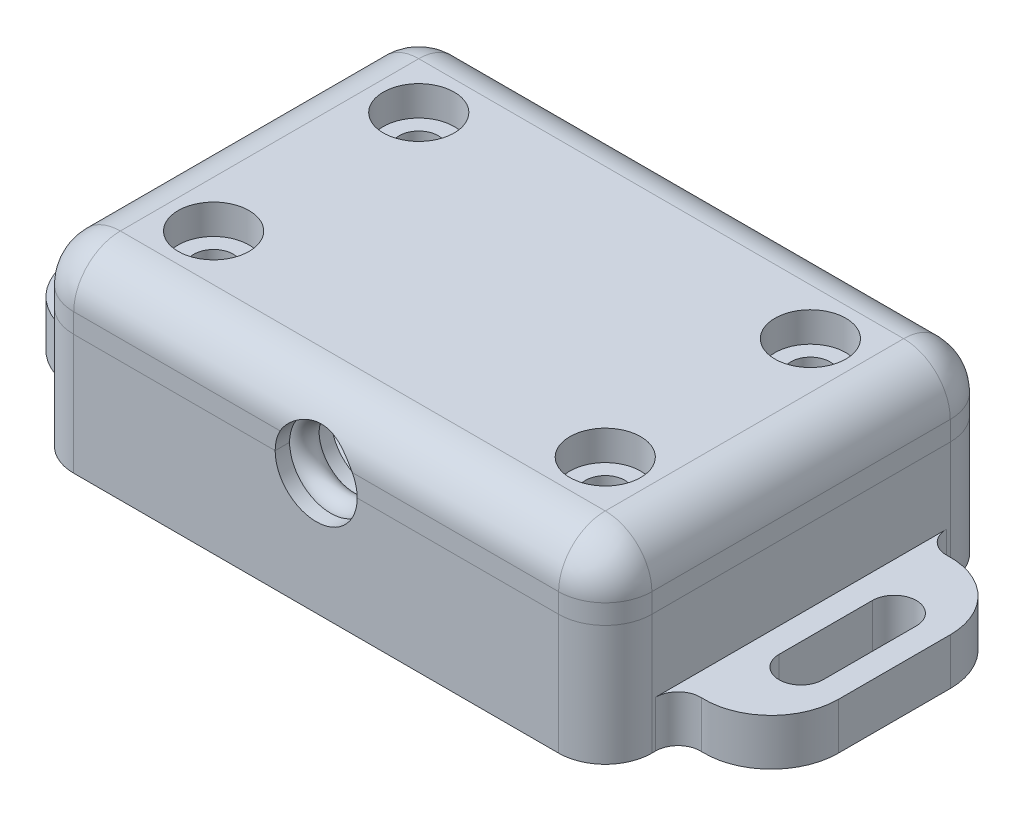
SolidWorks part; units mm, degrees
ref_plane "Front Plane" through (0, 0, 0) normal (0, 0, 1) x (1, 0, 0)
ref_plane "Top Plane" through (0, 0, 0) normal (0, 1, 0) x (1, 0, 0)
ref_plane "Right Plane" through (0, 0, 0) normal (1, 0, 0) x (0, 0, -1)
sketch "Sketch1" plane through (0, 0, 0) normal (0, 1, 0) x (1, 0, 0)
  line L5 (-15.875, -9.525) -> (15.875, -9.525)
  line L6 (-15.875, -9.525) -> (-15.875, 9.525)
  line L7 (-15.875, 9.525) -> (15.875, 9.525)
  line L8 (15.875, -9.525) -> (15.875, 9.525)
  line L9 (-15.875, -9.525) -> (15.875, 9.525) construction
  line L10 (-15.875, 9.525) -> (15.875, -9.525) construction
  line L11 (-19.685, -13.335) -> (19.685, -13.335)
  line L12 (-19.685, -13.335) -> (-19.685, 13.335)
  line L13 (-19.685, 13.335) -> (19.685, 13.335)
  line L14 (19.685, -13.335) -> (19.685, 13.335)
  line L15 (-19.685, -13.335) -> (19.685, 13.335) construction
  line L16 (-19.685, 13.335) -> (19.685, -13.335) construction
  point P0 (0, 0)
  point P6 (0, 0)
  dimension "D1" = 3.81
  dimension "D2" = 3.81
  dimension "D3" = 31.75
  dimension "D4" = 19.05
extrude "Boss-Extrude1" add sketch "Sketch1" along normal blind 4.2543
sketch "Sketch3" plane through (0, 0, 13.335) normal (0, 0, 1) x (1, 0, 0)
  line L0 (-19.685, 4.2543) -> (19.685, 4.2543) construction
  circle A0 centre (0, 4.2543) radius 2.794
  dimension "D1" = 5.588
extrude "Cut-Extrude1" cut sketch "Sketch3" against normal up to next
mirror "Mirror1" about plane through (0, 4.2543, 0) normal (0, -1, 0) of bodies 103
sketch "Sketch2" plane through (0, 0, 0) normal (0, -1, 0) x (1, 0, 0)
  line L0 (-19.685, 13.335) -> (19.685, 13.335) construction
  line L1 (19.685, -13.335) -> (-19.685, -13.335)
  line L2 (19.685, -13.335) -> (19.685, 13.335)
  line L3 (19.685, 13.335) -> (-19.685, 13.335)
  line L4 (-19.685, -13.335) -> (-19.685, 13.335)
  line L5 (19.685, -13.335) -> (-19.685, 13.335) construction
  line L6 (19.685, 13.335) -> (-19.685, -13.335) construction
  line L7 (-19.685, -13.335) -> (-19.685, 13.335) construction
  point P0 (0, 0)
extrude "Boss-Extrude2" add sketch "Sketch2" along normal blind 3.937
sketch "Sketch4" plane through (0, 4.2543, 0) normal (0, 1, 0) x (1, 0, 0)
  line L0 (2.794, -11.43) -> (16.51, -11.43)
  line L1 (2.794, -13.335) -> (2.794, -9.525) construction
  line L2 (17.78, -10.16) -> (17.78, 10.16)
  line L3 (16.51, 11.43) -> (-16.51, 11.43)
  line L4 (-17.78, 10.16) -> (-17.78, -10.16)
  line L5 (-16.51, -11.43) -> (-2.794, -11.43)
  line L6 (-2.794, -9.525) -> (-2.794, -13.335) construction
  line L7 (15.875, -9.525) -> (15.875, -11.43) construction
  line L8 (15.875, -11.43) -> (15.875, -9.525) construction
  line L9 (15.875, -9.525) -> (17.78, -9.525) construction
  line L10 (15.875, 9.525) -> (15.875, 11.43) construction
  line L11 (-15.875, 9.525) -> (-17.78, 9.525) construction
  arc A0 (16.51, -11.43) -> (17.78, -10.16) centre (16.51, -10.16) ccw
  arc A1 (-17.78, -10.16) -> (-16.51, -11.43) centre (-16.51, -10.16) ccw
  arc A2 (-16.51, 11.43) -> (-17.78, 10.16) centre (-16.51, 10.16) ccw
  arc A3 (17.78, 10.16) -> (16.51, 11.43) centre (16.51, 10.16) ccw
  dimension "D1" = 1.27
ref_plane "Plane1" through (2.794, 0, 0) normal (-1, 0, 0) x (0, 0, 1)
sketch "Sketch5" plane through (2.794, 0, 0) normal (-1, 0, 0) x (0, 0, 1)
  line L0 (13.335, 4.2543) -> (9.525, 4.2543) construction
  circle A0 centre (11.43, 4.2543) radius 0.9525
  dimension "D1" = 1.905
sketch "Sketch6" plane through (0, 4.2543, 0) normal (0, 1, 0) x (1, 0, 0)
  line L0 (-17.78, 10.16) -> (-17.78, -10.16) construction
  line L5 (16.51, 11.43) -> (-16.51, 11.43) construction
  line L6 (17.78, -10.16) -> (17.78, 10.16) construction
  line L7 (-17.78, 10.16) -> (-17.78, -10.16)
  line L8 (16.51, 11.43) -> (-16.51, 11.43)
  line L9 (17.78, -10.16) -> (17.78, 10.16)
  line L10 (-16.51, -11.43) -> (16.51, -11.43)
  arc A0 (-17.78, -10.16) -> (-16.51, -11.43) centre (-16.51, -10.16) ccw construction
  arc A1 (-16.51, 11.43) -> (-17.78, 10.16) centre (-16.51, 10.16) ccw construction
  arc A2 (17.78, 10.16) -> (16.51, 11.43) centre (16.51, 10.16) ccw construction
  arc A3 (16.51, -11.43) -> (17.78, -10.16) centre (16.51, -10.16) ccw construction
  arc A4 (-17.78, -10.16) -> (-16.51, -11.43) centre (-16.51, -10.16) ccw
  arc A5 (-16.51, 11.43) -> (-17.78, 10.16) centre (-16.51, 10.16) ccw
  arc A6 (17.78, 10.16) -> (16.51, 11.43) centre (16.51, 10.16) ccw
  arc A7 (16.51, -11.43) -> (17.78, -10.16) centre (16.51, -10.16) ccw
sweep "Cut-Sweep2" cut profiles "Sketch5" path "Sketch6"
sketch "Sketch7" plane through (0, 4.2543, 0) normal (0, 1, 0) x (1, 0, 0)
  line L0 (2.794, -10.4775) -> (16.51, -10.4775) construction
  line L1 (16.51, -12.3825) -> (2.794, -12.3825) construction
  line L2 (2.794, -10.4775) -> (2.794, -9.525) construction
  circle A0 centre (3.048, -11.43) radius 0.9525
  point P6 (3.1533, -13.906)
  dimension "D1" = 0.254
ref_axis "Axis1" through (0, 4.2543, 9.525) along (0, 0, 1)
revolve "Cut-Revolve1" cut sketch "Sketch7" angle 360 about axis through (0, 4.2543, 9.525) along (0, 0, 1)
sweep "Sweep1" add profiles "Sketch5<2>" path "Sketch4"
sketch "Sketch5<2>" plane through (2.794, 0, 0) normal (-1, 0, 0) x (0, 0, 1) same geometry as "Sketch5"
revolve "Revolve1" add sketch "Sketch7<2>" angle 360 about axis through (0, 4.2543, 9.525) along (0, 0, 1)
sketch "Sketch7<2>" plane through (0, 4.2543, 0) normal (0, 1, 0) x (1, 0, 0) same geometry as "Sketch7"
ref_plane "Top of PCB" through (0, 1.6, 0) normal (0, 1, 0) x (1, 0, 0)
sketch "Sketch9" plane through (0, 8.5086, 0) normal (0, 1, 0) x (1, 0, 0)
  line L0 (-19.685, -13.335) -> (19.685, -13.335) construction
  line L1 (19.685, 13.335) -> (-19.685, 13.335)
  line L2 (19.685, 13.335) -> (19.685, -13.335)
  line L3 (19.685, -13.335) -> (-19.685, -13.335)
  line L4 (-19.685, 13.335) -> (-19.685, -13.335)
  line L5 (19.685, 13.335) -> (-19.685, -13.335) construction
  line L6 (19.685, -13.335) -> (-19.685, 13.335) construction
  line L7 (-19.685, 13.335) -> (-19.685, -13.335) construction
  point P0 (0, 0)
extrude "Boss-Extrude3" add sketch "Sketch9" along normal blind 0.254
sketch "Sketch13" plane through (0, 8.5086, 0) normal (0, -1, 0) x (1, 0, 0)
  line L1 (15.875, -9.525) -> (-15.875, -9.525)
  line L2 (15.875, -9.525) -> (15.875, 9.525)
  line L3 (15.875, 9.525) -> (-15.875, 9.525)
  line L4 (-15.875, -9.525) -> (-15.875, 9.525)
  line L5 (15.875, -9.525) -> (-15.875, 9.525) construction
  line L6 (15.875, 9.525) -> (-15.875, -9.525) construction
  point P0 (0, 0)
extrude "Boss-Extrude5" add sketch "Sketch13" along normal blind 1.6
sketch "Sketch10" plane through (0, 6.9086, 0) normal (0, -1, 0) x (1, 0, 0)
  line L1 (15.875, -9.525) -> (-15.875, -9.525) construction
  line L2 (0, 0) -> (0, -50000) construction
  line L3 (0, 0) -> (-50000, 0) construction
  line L8 (13.335, -3.937) -> (15.875, -3.937)
  line L9 (10.287, -6.985) -> (10.287, -9.525)
  line L10 (10.287, -9.525) -> (15.875, -9.525)
  line L11 (15.875, -9.525) -> (15.875, -3.937)
  line L12 (-15.875, -9.525) -> (-15.875, -3.937)
  line L13 (-10.287, -9.525) -> (-15.875, -9.525)
  line L14 (-10.287, -6.985) -> (-10.287, -9.525)
  line L15 (-13.335, -3.937) -> (-15.875, -3.937)
  line L16 (-13.335, 3.937) -> (-15.875, 3.937)
  line L17 (-10.287, 6.985) -> (-10.287, 9.525)
  line L18 (-10.287, 9.525) -> (-15.875, 9.525)
  line L19 (-15.875, 9.525) -> (-15.875, 3.937)
  line L20 (15.875, 9.525) -> (15.875, 3.937)
  line L21 (10.287, 9.525) -> (15.875, 9.525)
  line L22 (10.287, 6.985) -> (10.287, 9.525)
  line L23 (13.335, 3.937) -> (15.875, 3.937)
  line L24 (15.875, 9.525) -> (15.875, -9.525) construction
  arc A0 (13.335, -3.937) -> (10.287, -6.985) centre (13.335, -6.985) ccw
  arc A1 (-13.335, -3.937) -> (-10.287, -6.985) centre (-13.335, -6.985) cw
  arc A2 (-13.335, 3.937) -> (-10.287, 6.985) centre (-13.335, 6.985) ccw
  arc A3 (13.335, 3.937) -> (10.287, 6.985) centre (13.335, 6.985) cw
  dimension "D3" = 3.048
  dimension "D1" = 2.54
  dimension "D2" = 2.54
extrude "Boss-Extrude4" add sketch "Sketch10" along normal up to surface (5.3086 mm away) up to plane "Top of PCB"
sketch "Sketch11" plane through (0, 1.6, 0) normal (0, -1, 0) x (1, 0, 0)
  line L0 (0, 0) -> (0, 50000) construction
  line L1 (0, 0) -> (50000, 0) construction
  circle A0 centre (13.335, 6.985) radius 1.3335
  circle A2 centre (13.335, -6.985) radius 1.3335
  circle A3 centre (-13.335, 6.985) radius 1.3335
  circle A4 centre (-13.335, -6.985) radius 1.3335
  arc A5 (10.287, 6.985) -> (13.335, 3.937) centre (13.335, 6.985) ccw construction
  dimension "D1" = 2.667
extrude "Cut-Extrude2" cut sketch "Sketch11" against normal through all
sketch "Sketch12" plane through (0, 8.7626, 0) normal (0, 1, 0) x (1, 0, 0)
  line L0 (0, 0) -> (0, -50000) construction
  line L1 (0, 0) -> (-50000, 0) construction
  circle A0 centre (-13.335, -6.985) radius 2.413
  circle A1 centre (-13.335, -6.985) radius 1.3335 construction
  circle A2 centre (-13.335, 6.985) radius 2.413
  circle A3 centre (13.335, -6.985) radius 2.413
  circle A4 centre (13.335, 6.985) radius 2.413
  dimension "D1" = 4.826
extrude "Cut-Extrude3" cut sketch "Sketch12" against normal blind 2.032
fillet "Fillet2" radius 3.175 8 edges at (19.685, 6.5085, -13.335) (-19.685, 6.5085, -13.335) (-19.685, 6.5085, 13.335) (19.685, 6.5085, 13.335) (19.685, 8.7626, 0) (0, 8.7626, -13.335) (-19.685, 8.7626, 0) (0, 8.7626, 13.335)
fillet "Fillet3" radius 3.175 12 edges at (10.287, 6.9086, 8.255) (14.605, 6.9086, 3.937) (14.605, 6.9086, -3.937) (10.287, 6.9086, -8.255) (-14.605, 6.9086, 3.937) (-10.287, 6.9086, 8.255) (-14.605, 6.9086, -3.937) (-11.1797, 6.9086, -4.8297) (11.1797, 6.9086, 4.8297) (11.1797, 6.9086, -4.8297) (-11.1797, 6.9086, 4.8297) (-10.287, 6.9086, -8.255)
fillet "Fillet4" radius 0.508 8 edges at (-13.081, 1.6, -9.525) (-15.875, 1.6, -6.731) (-15.875, 1.6, 6.731) (-13.081, 1.6, 9.525) (15.875, 1.6, 6.731) (13.081, 1.6, 9.525) (15.875, 1.6, -6.731) (13.081, 1.6, -9.525)
extrude "Cut-Extrude5" cut sketch "Sketch11<2>" along normal blind 4.572 draft 4
sketch "Sketch11<2>" plane through (0, 1.6, 0) normal (0, -1, 0) x (1, 0, 0) same geometry as "Sketch11"
fillet "Fillet5" radius 3.175 4 edges at (-19.685, 0.1586, -13.335) (-19.685, 0.1586, 13.335) (19.685, 0.1586, -13.335) (19.685, 0.1586, 13.335)
sketch "Sketch14" plane through (0, -3.937, 0) normal (0, -1, 0) x (1, 0, 0)
  line L0 (19.685, 9.9007) -> (19.685, -9.9007)
  line L1 (19.685, -10.16) -> (19.685, 10.16) construction
  line L3 (0, 0) -> (50000, 0) construction
  line L4 (26.035, -3.81) -> (26.035, 3.81)
  line L5 (22.86, 3.175) -> (22.86, -3.175) construction
  line L6 (24.36, 3.175) -> (24.36, -3.175)
  line L7 (21.36, 3.175) -> (21.36, -3.175)
  line L8 (22.86, -1.0957) -> (19.685, -1.0957) construction
  line L9 (19.685, -1.0957) -> (22.86, -1.0957) construction
  line L10 (22.86, -1.0957) -> (26.035, -1.0957) construction
  line L11 (0, 0) -> (0, 50000) construction
  line L12 (-22.86, 3.175) -> (-22.86, -3.175) construction
  line L13 (-24.36, 3.175) -> (-24.36, -3.175)
  line L14 (-21.36, 3.175) -> (-21.36, -3.175)
  line L15 (-22.86, -1.0957) -> (-26.035, -1.0957) construction
  line L16 (-19.685, -1.0957) -> (-22.86, -1.0957) construction
  line L17 (-22.86, -1.0957) -> (-19.685, -1.0957) construction
  line L18 (-26.035, -3.81) -> (-26.035, 3.81)
  line L19 (-19.685, 9.9007) -> (-19.685, -9.9007)
  arc A0 (19.685, -9.9007) -> (21.2725, -8.378) centre (21.209, -9.9007) cw
  arc A3 (21.2725, -8.378) -> (26.035, -3.81) centre (21.463, -3.81) ccw
  arc A4 (21.2725, 8.378) -> (26.035, 3.81) centre (21.463, 3.81) cw
  arc A5 (19.685, 9.9007) -> (21.2725, 8.378) centre (21.209, 9.9007) ccw
  arc A6 (24.36, 3.175) -> (21.36, 3.175) centre (22.86, 3.175) ccw
  arc A7 (21.36, -3.175) -> (24.36, -3.175) centre (22.86, -3.175) ccw
  arc A8 (-24.36, 3.175) -> (-21.36, 3.175) centre (-22.86, 3.175) cw
  arc A9 (-21.36, -3.175) -> (-24.36, -3.175) centre (-22.86, -3.175) cw
  arc A10 (-19.685, 9.9007) -> (-21.2725, 8.378) centre (-21.209, 9.9007) cw
  arc A11 (-21.2725, 8.378) -> (-26.035, 3.81) centre (-21.463, 3.81) ccw
  arc A12 (-21.2725, -8.378) -> (-26.035, -3.81) centre (-21.463, -3.81) cw
  arc A13 (-19.685, -9.9007) -> (-21.2725, -8.378) centre (-21.209, -9.9007) ccw
  point P7 (19.685, 0)
  point P17 (26.035, 0)
  point P19 (22.86, 0)
  point P31 (-22.86, 0)
  point P49 (-26.035, 0)
  point P50 (-19.685, 0)
  dimension "D1" = 1.524
  dimension "D2" = 4.572
  dimension "D6" = 1.5
  dimension "D3" = 6.35
  dimension "D4" = 7.62
  dimension "D5" = 6.35
extrude "Boss-Extrude6" add sketch "Sketch14" against normal blind 3.175
